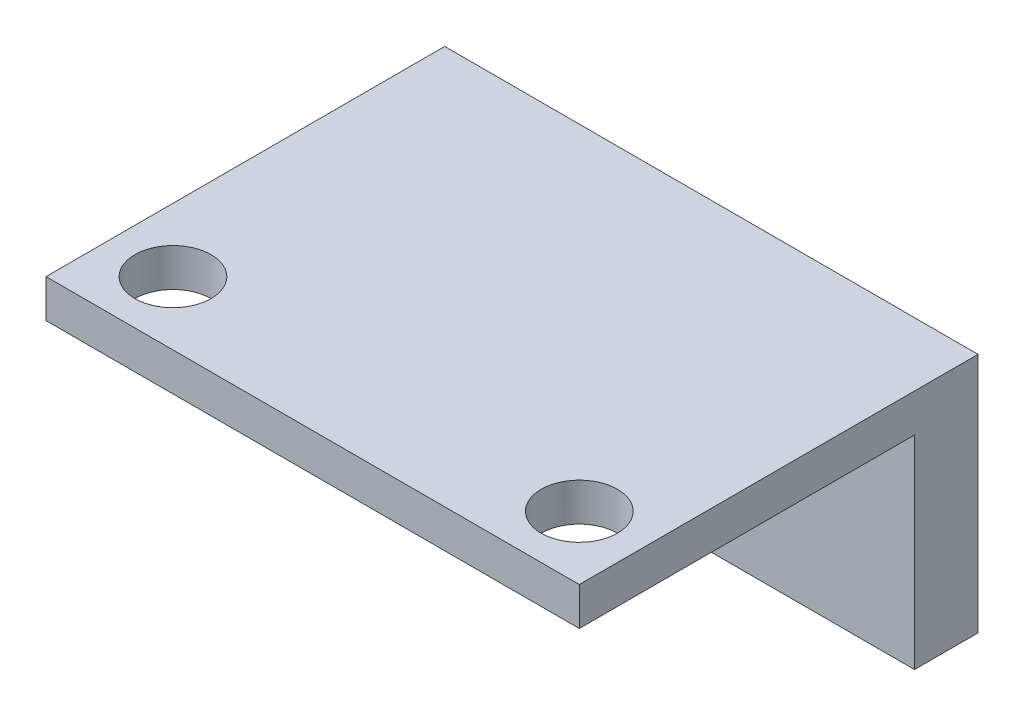
SolidWorks part; units mm, degrees
ref_plane "Front Plane" through (0, 0, 0) normal (0, 0, 1) x (1, 0, 0)
ref_plane "Top Plane" through (0, 0, 0) normal (0, 1, 0) x (1, 0, 0)
ref_plane "Right Plane" through (0, 0, 0) normal (1, 0, 0) x (0, 0, -1)
sketch "Sketch1" plane through (0, 0, 0) normal (0, 1, 0) x (1, 0, 0)
  line L1 (0, 0) -> (21, 0)
  line L2 (0, 0) -> (0, 15.7)
  line L3 (0, 15.7) -> (21, 15.7)
  line L4 (21, 0) -> (21, 15.7)
  dimension "D1" = 21
  dimension "D2" = 15.7
extrude "Boss-Extrude1" add sketch "Sketch1" along normal blind 1.5
sketch "Sketch2" plane through (0, 1.5, 0) normal (0, 1, 0) x (1, 0, 0)
  line L0 (0, 0) -> (21, 0) construction
  line L1 (0, 15.7) -> (0, 0) construction
  line L2 (21, 0) -> (21, 15.7) construction
  circle A0 centre (2.5, 2.5) radius 1.5
  circle A1 centre (18.5, 2.5) radius 1.5
  dimension "D1" = 3
  dimension "D2" = 2.5
  dimension "D3" = 2.5
  dimension "D4" = 2.5
extrude "Cut-Extrude1" cut sketch "Sketch2" against normal up to surface (1.5 mm away) up to face at (10.5, 0, -7.85)
sketch "Sketch3" plane through (0, 0, 0) normal (0, -1, 0) x (1, 0, 0)
  line L0 (21, 0) -> (21, -15.7) construction
  line L1 (0, -15.7) -> (21, -15.7)
  line L2 (0, -15.7) -> (0, -13.2)
  line L3 (0, -13.2) -> (21, -13.2)
  line L4 (21, -15.7) -> (21, -13.2)
  dimension "D1" = 2.5
extrude "Boss-Extrude2" add sketch "Sketch3" along normal blind 8
